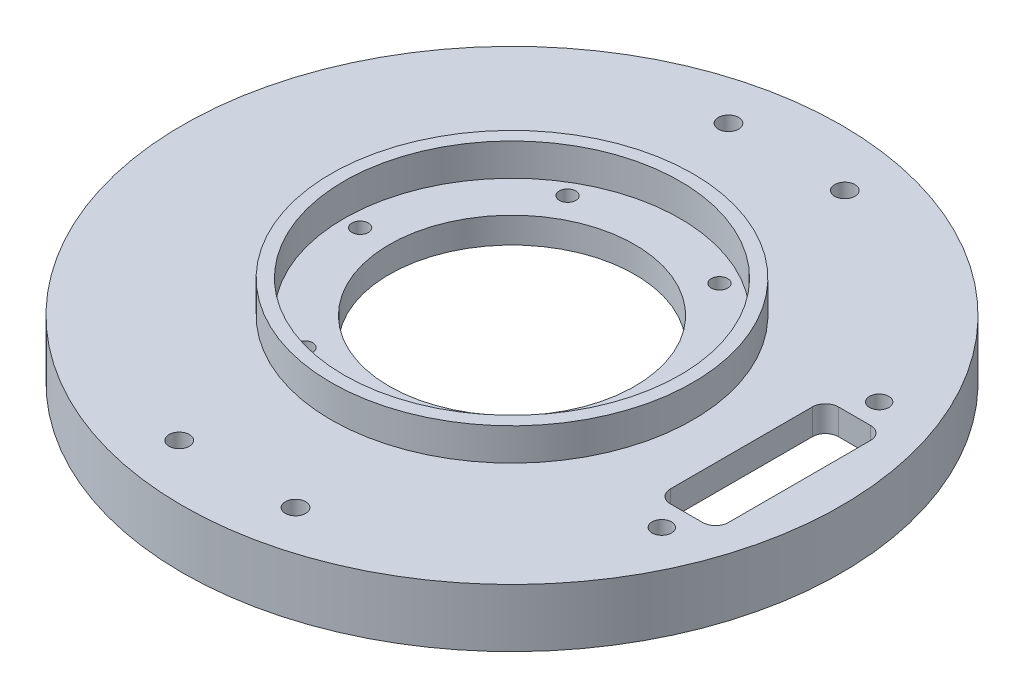
SolidWorks part; units mm, degrees
material "1060 Сплав"
ref_plane "Спереди" through (0, 0, 0) normal (0, 0, 1) x (1, 0, 0)
ref_plane "Сверху" through (0, 0, 0) normal (0, 1, 0) x (1, 0, 0)
ref_plane "Справа" through (0, 0, 0) normal (1, 0, 0) x (0, 0, -1)
sketch "Эскиз1" plane through (0, 0, 0) normal (0, 1, 0) x (1, 0, 0)
  circle A0 centre (0, 0) radius 19
  circle A1 centre (0, 0) radius 51
  dimension "D1" = 38
  dimension "D2" = 102
extrude "Бобышка-Вытянуть1" add sketch "Эскиз1" along normal blind 4
hole_wizard "Сверло под метчик  спиральное M2.51" positions "Эскиз2" profile "Эскиз3" hole size "M2.5x0.45" standard "DIN"
sketch "Эскиз2" plane through (0, 4, 0) normal (0, 1, 0) x (1, 0, 0)
  point P0 (23.5, 0)
  dimension "D1" = 23.5
sketch "Эскиз3" plane through (23.5, 4, 0) normal (1, 0, 0) x (0, 0, 1)
  line L0 (0, 0) -> (0, 8.7661)
  line L1 (0, 8.7661) -> (1.275, 8)
  line L2 (1.275, 8) -> (1.275, 0)
  line L5 (1.275, 0) -> (0, 0)
  line L10 (0, 8.7661) -> (-1.275, 8) construction
  line L11 (0, -6.35) -> (0, 107.95) construction
  dimension "Диаметр отверстия" = 2.55
  dimension "Глубина отверстия" = 8
  dimension "Угол заточки сверла" = 118
pattern_circular "Круговой массив1" count 6 over 360 about axis through (0, 4, 0) along (0, 1, 0) of "Сверло под метчик  спиральное M2.51"
hole_wizard "Сверло под метчик  спиральное M32" positions "Эскиз4" profile "Эскиз5" hole size "M3x0.5" standard "DIN" end condition through all
sketch "Эскиз4" plane through (0, 0, 0) normal (0, -1, 0) x (-1, 0, 0)
  point P0 (-9, -42.5)
  dimension "D1" = 9
  dimension "D2" = 42.5
sketch "Эскиз5" plane through (9, 0, 42.5) normal (1, 0, 0) x (0, 0, -1)
  line L0 (0, 0) -> (0, 4)
  line L1 (0, 4) -> (1.575, 4)
  line L2 (1.575, 4) -> (1.575, 0)
  line L5 (1.575, 0) -> (0, 0)
  line L11 (0, -6.35) -> (0, 107.95) construction
  dimension "Диаметр сквозного отверстия" = 3.15
  dimension "Глубина сквозного отверстия" = 4
sketch "Эскиз6" plane through (0, 0, 0) normal (0, 1, 0) x (1, 0, 0)
  line L0 (0, 0) -> (0, 15.2777) construction
  line L1 (0, 0) -> (-12.2514, 0) construction
pattern_linear "Линейный массив1" count 2 spacing 18 along (-1, 0, 0) count 2 spacing 85 along (0, 0, -1) of "Сверло под метчик  спиральное M32"
sketch "Эскиз14" plane through (0, 4, 0) normal (0, 1, 0) x (1, 0, 0)
  circle A0 centre (0, 0) radius 26
  circle A1 centre (0, 0) radius 28
  dimension "D1" = 52
  dimension "D2" = 56
extrude "Бобышка-Вытянуть2" add sketch "Эскиз14" along normal blind 5
sketch "Эскиз15" plane through (0, 0, 0) normal (0, -1, 0) x (1, 0, 0)
  circle A0 centre (0, 0) radius 51
  circle A1 centre (0, 0) radius 48
  dimension "D1" = 102
  dimension "D2" = 96
extrude "Бобышка-Вытянуть3" add sketch "Эскиз15" along normal blind 5
sketch "Эскиз16" plane through (0, 4, 0) normal (0, 1, 0) x (1, 0, 0)
  line L0 (0, 0) -> (47.3, 0) construction
  line L2 (44.5, -13) -> (35.5, -13)
  line L3 (44.5, -13) -> (44.5, 13)
  line L4 (44.5, 13) -> (35.5, 13)
  line L5 (35.5, -13) -> (35.5, 13)
  line L6 (44.5, -13) -> (35.5, 13) construction
  line L7 (44.5, 13) -> (35.5, -13) construction
  circle A0 centre (40, 16.82) radius 1.5
  circle A1 centre (40, -16.82) radius 1.5
  point P3 (40, 0)
  point P12 (0, 0)
  dimension "D4" = 3
  dimension "D5" = 3
  dimension "D1" = 40
  dimension "D2" = 9
  dimension "D3" = 26
  dimension "D6" = 16.82
  dimension "D7" = 33.64
extrude "Вырез-Вытянуть1" cut sketch "Эскиз16" against normal through all
fillet "Скругление1" radius 2 4 edges at (44.5, 2, 13) (35.5, 2, 13) (44.5, 2, -13) (35.5, 2, -13)
